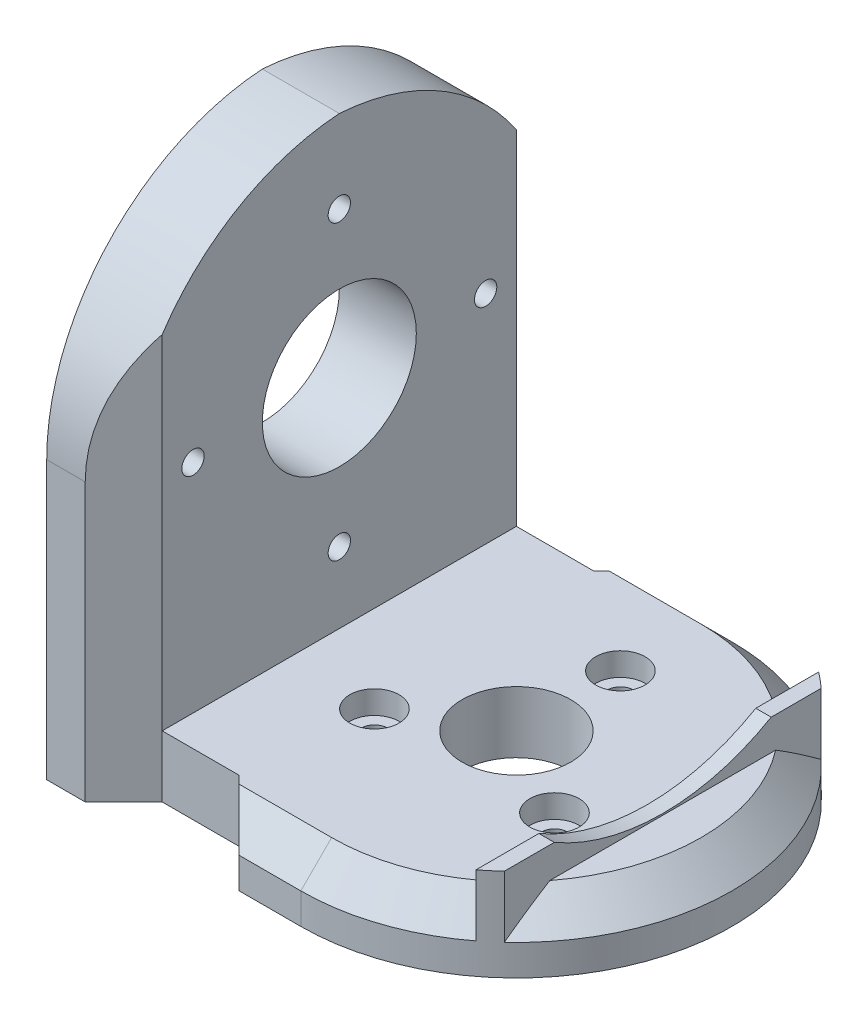
SolidWorks part; units mm, degrees
ref_plane "前视基准面" through (0, 0, 0) normal (0, 0, 1) x (1, 0, 0)
ref_plane "上视基准面" through (0, 0, 0) normal (0, 1, 0) x (1, 0, 0)
ref_plane "右视基准面" through (0, 0, 0) normal (1, 0, 0) x (0, 0, -1)
sketch "草图1" plane through (0, 0, 0) normal (0, 1, 0) x (1, 0, 0)
  line L0 (-23, 28) -> (-33, 28)
  line L1 (-23, 28) -> (0, 28)
  line L2 (-23, 28) -> (-23, -28) construction
  line L3 (-23, -28) -> (0, -28)
  line L4 (23, 28) -> (23, -28) construction
  line L5 (-33, 28) -> (-33, -28)
  line L6 (-33, -28) -> (-23, -28)
  arc A0 (0, -28) -> (0, 28) centre (0, 0) ccw
  circle A1 centre (0, 0) radius 13.5 construction
  circle A2 centre (0, 13.5) radius 1.7
  circle A3 centre (11.6913, -6.75) radius 1.7
  circle A4 centre (-11.6913, -6.75) radius 1.7
  circle A5 centre (0, 0) radius 7.0467
  point P12 (0, 0)
  dimension "D2" = 56
  dimension "D3" = 27
  dimension "D4" = 3.4
  dimension "D5" = 46
  dimension "D6" = 56
  dimension "D7" = 23
  dimension "D8" = 28
  dimension "D9" = 10
  dimension "D1" = 3
extrude "凸台-拉伸2" add sketch "草图1" along normal blind 8
sketch "草图2" plane through (0, 8, 0) normal (0, 1, 0) x (1, 0, 0)
  line L1 (-33, 28) -> (-23, 28)
  line L2 (-33, 28) -> (-33, -28)
  line L3 (-33, -28) -> (-23, -28)
  line L4 (-23, 28) -> (-23, -28)
  dimension "D1" = 10
extrude "凸台-拉伸3" add sketch "草图2" along normal blind 58
sketch "草图3" plane through (-23, 0, 0) normal (1, 0, 0) x (0, 0, -1)
  line L2 (-28, 66) -> (-28, 8) construction
  line L3 (-28, 8) -> (28, 8) construction
  circle A0 centre (0, 36.2) radius 28 construction
  circle A1 centre (0, 36.2) radius 19 construction
  circle A2 centre (0, 55.2) radius 1.45
  circle A3 centre (19, 36.2) radius 1.45
  circle A4 centre (0, 17.2) radius 1.45
  circle A5 centre (-19, 36.2) radius 1.45
  circle A6 centre (0, 36.2) radius 10
  point P14 (0, 36.2)
  dimension "D1" = 56
  dimension "D2" = 38
  dimension "D3" = 2.9
  dimension "D4" = 4
  dimension "D5" = 20
  dimension "D6" = 28
  dimension "D7" = 28.2
extrude "切除-拉伸1" cut sketch "草图3" against normal blind 22
sketch "草图5" plane through (0, 8, 0) normal (0, 1, 0) x (1, 0, 0)
  line L0 (31.6695, 0) -> (-34.9539, 0) construction
  line L1 (-23, -19) -> (-23, 19) construction
  line L2 (-23, 23) -> (-13, 23)
  line L3 (-23, 23) -> (-23, 43.3671)
  line L4 (-23, 43.3671) -> (-13, 43.3671)
  line L5 (-13, 23) -> (-13, 43.3671)
  line L6 (0, 28) -> (-23, 28) construction
  line L7 (-13, -23) -> (-13, -43.3671)
  line L8 (-23, -43.3671) -> (-13, -43.3671)
  line L9 (-23, -23) -> (-23, -43.3671)
  line L10 (-23, -23) -> (-13, -23)
  dimension "D1" = 10
  dimension "D2" = 5
extrude "切除-拉伸3" cut sketch "草图5" against normal blind 18
chamfer "倒角1" distance 5 angle 45 4 edges at (-23, 33, 28) (-23, 33, -28) (-13, 4, -28) (-13, 4, 28)
fillet "圆角1" radius 30 2 edges at (-30.5, 66, -28) (-30.5, 66, 28)
sketch "草图6" plane through (-33, 0, 0) normal (-1, 0, 0) x (0, 0, 1)
  circle A0 centre (-19, 36.2) radius 3.2
  circle A1 centre (0, 55.2) radius 3.2
  circle A2 centre (19, 36.2) radius 3.2
  circle A3 centre (0, 17.2) radius 3.2
  point P12 (0, 36.2)
  dimension "D1" = 6.4
  dimension "D2" = 4
extrude "切除-拉伸4" cut sketch "草图6" against normal blind 4
sketch "草图7" plane through (0, 8, 0) normal (0, 1, 0) x (1, 0, 0)
  circle A0 centre (0, 13.5) radius 3.2
  circle A1 centre (11.6913, -6.75) radius 3.2
  circle A2 centre (-11.6913, -6.75) radius 3.2
  point P9 (0, 0)
  dimension "D1" = 6.4
  dimension "D2" = 3
extrude "切除-拉伸5" cut sketch "草图7" against normal blind 3
sketch "草图8" plane through (0, 8, 0) normal (0, 1, 0) x (1, 0, 0)
  line L0 (-23, -23) -> (-23, 23) construction
  line L2 (17, -22.2486) -> (17, 22.2486)
  line L4 (19, -20.567) -> (19, 20.567)
  arc A0 (17, -22.2486) -> (19, -20.567) centre (0, 0) ccw
  arc A1 (19, 20.567) -> (17, 22.2486) centre (0, 0) ccw
  dimension "D4" = 40
extrude "凸台-拉伸4" add sketch "草图8" along normal blind 4
sketch "草图9" plane through (19, 0, 0) normal (1, 0, 0) x (0, 0, -1)
  circle A0 centre (0, 36.2) radius 28
  dimension "D1" = 56
extrude "切除-拉伸6" cut sketch "草图9" against normal blind 10
chamfer "倒角2" distance 4 angle 45 5 edges at (-4, 8, 28) (8.9733, 8, 26.5232) (28, 8, 0) (-4, 8, -28) (8.9733, 8, -26.5232)
